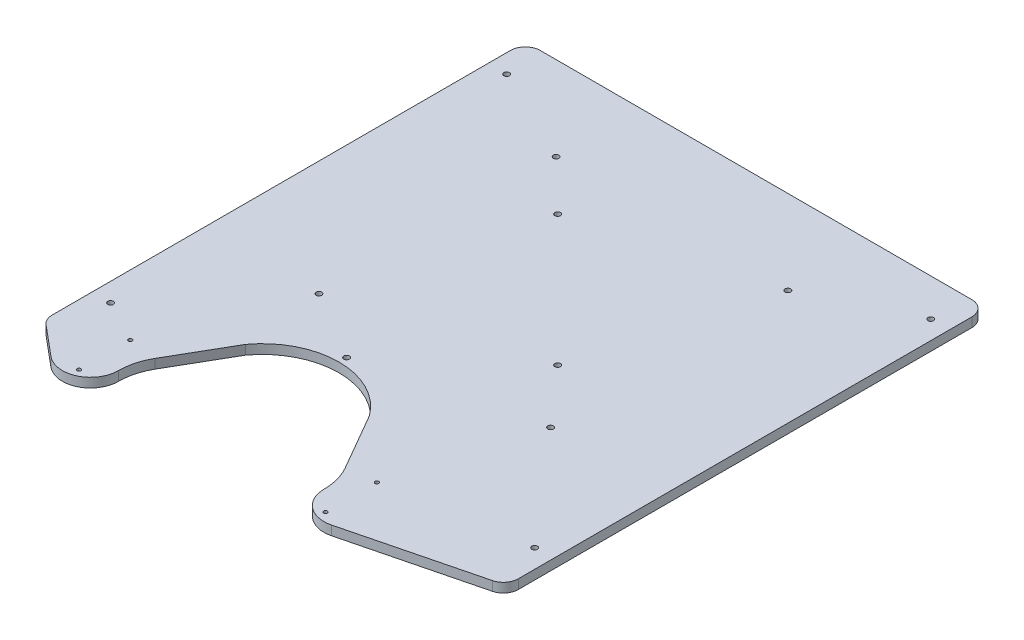
SolidWorks part; units mm, degrees
material "ABS PC"
ref_plane "Plan de face" through (0, 0, 0) normal (0, 0, 1) x (1, 0, 0)
ref_plane "Plan de dessus" through (0, 0, 0) normal (0, 1, 0) x (1, 0, 0)
ref_plane "Plan de droite" through (0, 0, 0) normal (1, 0, 0) x (0, 0, -1)
sketch "Esquisse1" plane through (0, 0, 0) normal (0, 1, 0) x (1, 0, 0)
  line L0 (-60.6815, -188.3301) -> (-75.8539, -214.6094) construction
  line L1 (-115.5, 31.2) -> (115.5, 31.2)
  line L2 (-123.5, 23.2) -> (-123.5, -222.0619)
  line L3 (-60.6815, -188.3301) -> (-75.8539, -214.6094)
  line L4 (123.5, 23.2) -> (123.5, -219.5635)
  line L5 (25.8539, -214.6094) -> (10.6815, -188.3301) construction
  line L6 (25.8539, -214.6094) -> (10.6815, -188.3301)
  line L7 (8.1815, -184) -> (10.6815, -188.3301)
  line L8 (-58.1815, -184) -> (-60.6815, -188.3301)
  line L9 (-120.6327, -228.1983) -> (-104.6238, -241.5886)
  line L10 (117.4519, -227.3217) -> (48.6599, -244.6295)
  line L12 (-108.5, -220.8) -> (-118.5, -220.8) construction
  line L15 (-118.5, -220.8) -> (-118.5, 31.2) construction
  line L16 (118.5, -220.8) -> (118.5, 31.2) construction
  line L18 (108.5, 31.2) -> (-108.5, 31.2) construction
  arc A0 (8.1815, -184) -> (-58.1815, -184) centre (-25, -208.0829) ccw construction
  arc A1 (8.1815, -184) -> (-58.1815, -184) centre (-25, -208.0829) ccw
  circle A2 centre (-91, -240.25) radius 1.95 construction
  arc A4 (30, -230.0829) -> (45, -245.0829) centre (45, -230.0829) ccw construction
  arc A5 (30, -230.0829) -> (25.8539, -214.6094) centre (-0.9469, -230.0829) ccw construction
  arc A6 (30, -230.0829) -> (25.8539, -214.6094) centre (-0.9469, -230.0829) ccw
  arc A7 (-95, -245.0829) -> (-80, -230.0829) centre (-95, -230.0829) ccw construction
  circle A8 centre (41, -212.75) radius 1
  circle A9 centre (41, -240.25) radius 1
  arc A10 (-115.5, 31.2) -> (-123.5, 23.2) centre (-115.5, 23.2) ccw
  arc A11 (115.5, 31.2) -> (123.5, 23.2) centre (115.5, 23.2) cw
  arc A12 (117.4519, -227.3217) -> (123.5, -219.5635) centre (115.5, -219.5635) ccw
  arc A13 (-123.5, -222.0619) -> (-120.6327, -228.1983) centre (-115.5, -222.0619) ccw
  arc A14 (-87.0138, -242.7801) -> (-80, -230.0829) centre (-95, -230.0829) ccw
  arc A15 (-75.8539, -214.6094) -> (-80, -230.0829) centre (-49.0531, -230.0829) ccw construction
  arc A16 (-75.8539, -214.6094) -> (-80, -230.0829) centre (-49.0531, -230.0829) ccw
  arc A17 (30, -230.0829) -> (42.3384, -244.8448) centre (45, -230.0829) ccw
  arc A18 (42.3384, -244.8448) -> (48.6599, -244.6295) centre (45, -230.0829) ccw
  arc A19 (-87.0138, -242.7801) -> (-104.6238, -241.5886) centre (-95, -230.0829) cw
  circle A20 centre (-91, -212.75) radius 1
  circle A21 centre (-91, -240.25) radius 1
  point P31 (-123.5, -225.8)
  point P44 (123.5, -225.8)
  dimension "D2" = 2
  dimension "D6" = 8
  dimension "D3" = 5
  dimension "D4" = 5
  dimension "D5" = 5
extrude "Boss.-Extru.1" add sketch "Esquisse1" against normal blind 5
sketch "Esquisse2" plane through (0, 0, 0) normal (0, 1, 0) x (1, 0, 0)
  circle A0 centre (-113.5, 11.2) radius 1.5
  circle A1 centre (-25, -163) radius 1.5
  circle A2 centre (113.5, 11.2) radius 1.5
  circle A3 centre (113.5, -200.8) radius 1.5
  circle A4 centre (-113.5, -200.8) radius 1.5
  dimension "D1" = 3
extrude "Enlèv. mat.-Extru.1" cut sketch "Esquisse2" against normal through all
sketch "Esquisse3" plane through (0, 0, 0) normal (0, 1, 0) x (1, 0, 0)
  circle A0 centre (62, -140.8) radius 1.5 construction
  circle A1 centre (62, -140.8) radius 1.5
  circle A2 centre (-62, -140.8) radius 1.5 construction
  circle A3 centre (-62, -140.8) radius 1.5
  circle A4 centre (62, -13.8) radius 1.5 construction
  circle A5 centre (62, -13.8) radius 1.5
  circle A6 centre (-62, -13.8) radius 1.5 construction
  circle A7 centre (-62, -13.8) radius 1.5
extrude "Enlèv. mat.-Extru.2" cut sketch "Esquisse3" against normal through all
sketch "Esquisse4" plane through (0, 0, 0) normal (0, 1, 0) x (1, 0, 0)
  circle A0 centre (-35, -40) radius 1.5 construction
  circle A1 centre (-35, -40) radius 1.5
  circle A2 centre (35, -110) radius 1.5 construction
  circle A3 centre (35, -110) radius 1.5
extrude "Enlèv. mat.-Extru.3" cut sketch "Esquisse4" against normal through all
